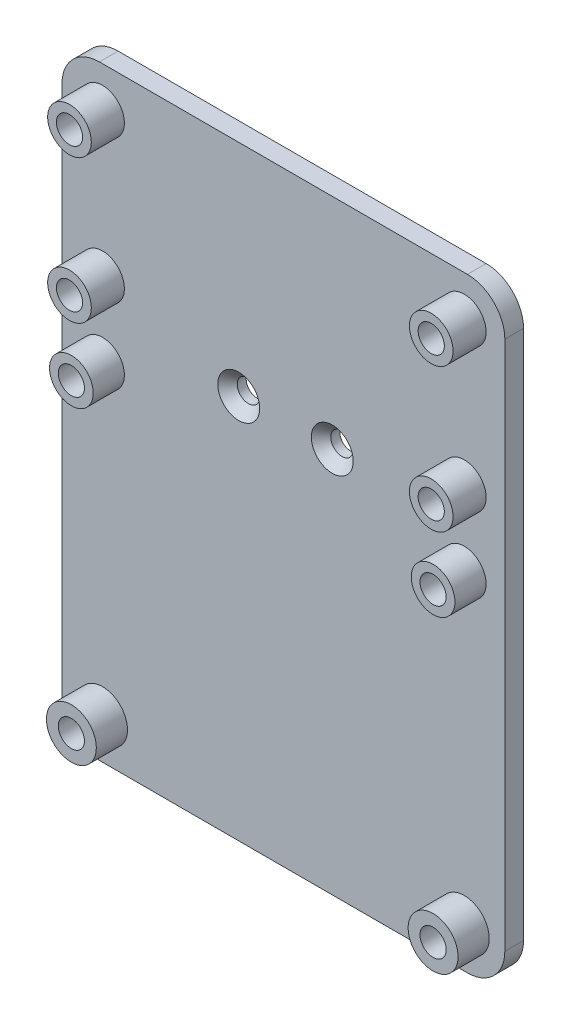
SolidWorks part; units mm, degrees
material "ABS"
ref_plane "Front Plane" through (0, 0, 0) normal (0, 0, 1) x (1, 0, 0)
ref_plane "Top Plane" through (0, 0, 0) normal (0, 1, 0) x (1, 0, 0)
ref_plane "Right Plane" through (0, 0, 0) normal (1, 0, 0) x (0, 0, -1)
sketch "Sketch1" plane through (0, 0, 0) normal (0, 0, 1) x (1, 0, 0)
  line L0 (0.5, 3.5) -> (-78.4242, 3.5)
  line L1 (-81.4242, 0.5) -> (-81.4242, -49.5)
  line L2 (-78.4242, -52.5) -> (0.5, -52.5)
  line L3 (3.5, -49.5) -> (3.5, 0.5)
  line L4 (-58.5, 8.5) -> (0.5, 8.5)
  line L5 (3.5, 11.5) -> (3.5, 35.5)
  line L6 (0.5, 38.5) -> (-58.5, 38.5)
  line L7 (-61.5, 35.5) -> (-61.5, 11.5)
  line L8 (-84.4242, 0.5) -> (-84.4242, -49.5)
  line L9 (-78.4242, -55.5) -> (0.5, -55.5)
  line L10 (6.5, -49.5) -> (6.5, 0.5)
  line L11 (6.5, 11.5) -> (6.5, 35.5)
  line L12 (0.5, 41.5) -> (-58.5, 41.5)
  line L13 (6.5, 11.5) -> (6.5, 0.5)
  line L14 (-70.5, 6.5) -> (-78.4242, 6.5)
  line L15 (-64.5, 35.5) -> (-64.5, 12.5)
  line L17 (-64.5, 35.5) -> (-64.5, 11.5) construction
  line L18 (0.5, 6.5) -> (-78.4242, 6.5) construction
  arc A0 (3.5, 0.5) -> (0.5, 3.5) centre (0.5, 0.5) ccw
  arc A1 (-78.4242, 3.5) -> (-81.4242, 0.5) centre (-78.4242, 0.5) ccw
  arc A2 (-81.4242, -49.5) -> (-78.4242, -52.5) centre (-78.4242, -49.5) ccw
  arc A3 (0.5, -52.5) -> (3.5, -49.5) centre (0.5, -49.5) ccw
  arc A4 (-61.5, 11.5) -> (-58.5, 8.5) centre (-58.5, 11.5) ccw
  arc A5 (0.5, 8.5) -> (3.5, 11.5) centre (0.5, 11.5) ccw
  arc A6 (3.5, 35.5) -> (0.5, 38.5) centre (0.5, 35.5) ccw
  arc A7 (-58.5, 38.5) -> (-61.5, 35.5) centre (-58.5, 35.5) ccw
  circle A8 centre (-58, 0) radius 1.375
  circle A9 centre (-58, -49) radius 1.375
  circle A10 centre (0, -49) radius 1.375
  circle A11 centre (0, 0) radius 1.375
  circle A12 centre (0, 12) radius 1.375
  circle A13 centre (0, 35) radius 1.375
  circle A14 centre (-58, 35) radius 1.375
  circle A15 centre (-58, 12) radius 1.375
  arc A16 (-84.4242, -49.5) -> (-78.4242, -55.5) centre (-78.4242, -49.5) ccw
  arc A17 (0.5, -55.5) -> (6.5, -49.5) centre (0.5, -49.5) ccw
  arc A18 (6.5, 35.5) -> (0.5, 41.5) centre (0.5, 35.5) ccw
  arc A19 (-58.5, 41.5) -> (-64.5, 35.5) centre (-58.5, 35.5) ccw
  arc A20 (-78.4242, 6.5) -> (-84.4242, 0.5) centre (-78.4242, 0.5) ccw
  arc A21 (-64.5, 12.5) -> (-70.5, 6.5) centre (-70.5, 12.5) cw
  dimension "D5" = 6
  dimension "D1" = 24
  dimension "D2" = 3
  dimension "D3" = 3
  dimension "D4" = 3
extrude "Boss-Extrude1" add sketch "Sketch1" along normal blind 3 contours L15 A21 L14 A20 L8 A16 L9 A17 L10 L13 L11 A18 L12 A19 A3 L2 A2 L1 A1 L0 A0 L3 A7 L6 A6 L5 A5 L4 A4 L7 | L6 A7 L7 A4 L4 A5 L5 A6 A15 A14 A13 A12 | L2 A3 L3 A0 L0 A1 L1 A2 A11 A10 A9 A8 region at (-39.0122, -24.5, 0) region at (-29, 23.5, 0) region at (-81.7267, 3.8025, 0)
sketch "Sketch2" plane through (0, 0, 3) normal (0, 0, 1) x (1, 0, 0)
  circle A1 centre (-58, 35) radius 3.5
  circle A2 centre (-58, 12) radius 3.5
  circle A3 centre (0, 35) radius 3.5
  circle A4 centre (0, 12) radius 3.5
  circle A5 centre (-58, -49) radius 4
  circle A6 centre (0, -49) radius 4
  circle A7 centre (0, 0) radius 3.5
  circle A8 centre (-58, 0) radius 3.5
  circle M13 centre (-58, 12) radius 1.375
  circle M14 centre (-58, 35) radius 1.375
  circle M15 centre (0, 35) radius 1.375
  circle M16 centre (0, 12) radius 1.375
  circle M17 centre (0, 0) radius 1.375
  circle M18 centre (0, -49) radius 1.375
  circle M19 centre (-58, -49) radius 1.375
  circle M20 centre (-58, 0) radius 1.375
  dimension "D1" = 7
  dimension "D2" = 7
  dimension "D3" = 7
  dimension "D4" = 7
  dimension "D5" = 7
  dimension "D6" = 7
  dimension "D7" = 8
  dimension "D8" = 8
extrude "Boss-Extrude2" add sketch "Sketch2" along normal blind 5 contours A8 M20 | A7 M17 | A6 M18 | A5 M19 region at (-61.8869, -49, 3) region at (-3.8869, -49, 3) region at (-3.401, 0, 3) region at (-61.401, 0, 3)
extrude "Boss-Extrude3" add sketch "Sketch2<3>" along normal blind 5.3 contours A1 M14 | A2 M13 | A3 M15 | A4 M16 region at (-61.401, 35, 3) region at (-61.401, 12, 3) region at (-3.401, 35, 3) region at (-3.401, 12, 3)
sketch "Sketch2<3>" plane through (0, 0, 3) normal (0, 0, 1) x (1, 0, 0) same geometry as "Sketch2"
sketch "Sketch3" plane through (0, 0, 8.3) normal (0, 0, 1) x (1, 0, 0)
  circle A0 centre (-58, 35) radius 2.1
  circle A1 centre (0, 35) radius 2.1
  circle A2 centre (0, 12) radius 2.1
  circle A3 centre (-58, 12) radius 2.1
  circle A4 centre (-58, 0) radius 2.1
  circle A5 centre (0, 0) radius 2.1
  circle A6 centre (-58, -49) radius 2.1
  circle A7 centre (0, -49) radius 2.1
extrude "Cut-Extrude1" cut sketch "Sketch3" against normal through all
hole_wizard "CSK for M3 Hex Socket Countersunk Cap Screw1" positions "Sketch4" profile "Sketch5" countersink size "M3" standard "ISO"
sketch "Sketch4" plane through (0, 0, 3) normal (0, 0, 1) x (1, 0, 0)
  point P0 (-36.1638, 6.2259)
  point P2 (-21.1647, 6.3944)
  dimension "D1" = 15
sketch "Sketch5" plane through (-36.1638, 6.2259, 3) normal (1, 0, 0) x (0, -1, 0)
  line L0 (0, 0) -> (0, 15.5215)
  line L1 (0, 15.5215) -> (1.8, 14.44)
  line L2 (1.8, 14.44) -> (1.8, 1.56)
  line L3 (1.8, 1.56) -> (3.36, 0)
  line L5 (3.36, 0) -> (0, 0)
  line L6 (-1.8, 1.56) -> (-3.36, 0) construction
  line L10 (0, 15.5215) -> (-1.8, 14.44) construction
  line L11 (0, -6.35) -> (0, 107.95) construction
  dimension "Hole Dia." = 3.6
  dimension "Hole Depth" = 14.44
  dimension "Near C'Sink Dia." = 6.72
  dimension "Near C'Sink Angle" = 90
  dimension "Drill Angle" = 118
sketch "Sketch6" plane through (0, 0, 3) normal (0, 0, 1) x (1, 0, 0)
  line L0 (-64.5, 12.5) -> (-64.5, -55.5)
  line L1 (-78.4242, -55.5) -> (0.5, -55.5) construction
  line L2 (-64.5, -55.5) -> (-104.8112, -55.5)
  line L3 (-104.8112, -55.5) -> (-104.8112, 12.5)
  line L4 (-104.8112, 12.5) -> (-64.5, 12.5)
extrude "Cut-Extrude2" cut sketch "Sketch6" against normal through all
fillet "Fillet1" radius 6 1 edges at (-64.5, -55.5, 1.5)
